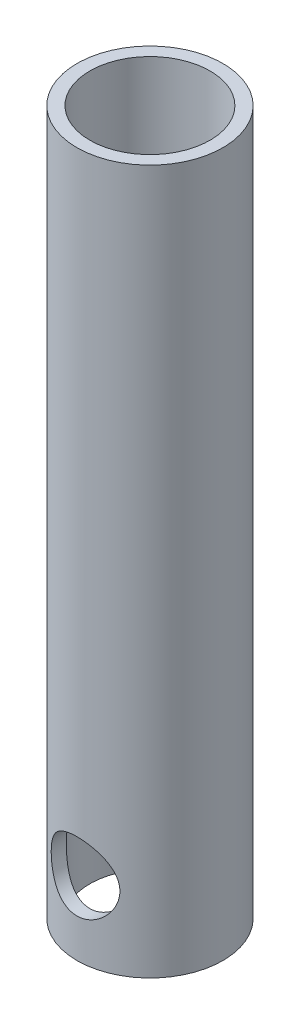
SolidWorks part; units mm, degrees
material "Plain Carbon Steel"
ref_plane "Front" through (0, 0, 0) normal (0, 0, 1) x (1, 0, 0)
ref_plane "Top" through (0, 0, 0) normal (0, 1, 0) x (1, 0, 0)
ref_plane "Right" through (0, 0, 0) normal (1, 0, 0) x (0, 0, -1)
sketch "Sketch1" plane through (0, 0, 0) normal (0, 1, 0) x (1, 0, 0)
  circle A0 centre (0, 0) radius 14
  circle A1 centre (0, 0) radius 17
  dimension "D1" = 28
  dimension "D2" = 34
extrude "Boss-Extrude1" add sketch "Sketch1" along normal blind 164
sketch "Sketch2" plane through (0, 0, 0) normal (0, 0, 1) x (1, 0, 0)
  line L0 (-17, 0) -> (17, 0) construction
  circle A0 centre (0, 17) radius 8
  dimension "D1" = 16
  dimension "D2" = 17
extrude "Cut-Extrude1" cut sketch "Sketch2" against normal through all both and the other way through all
ref_axis "Axis1" through (0, 17, -17) along (0, 0, 1)
